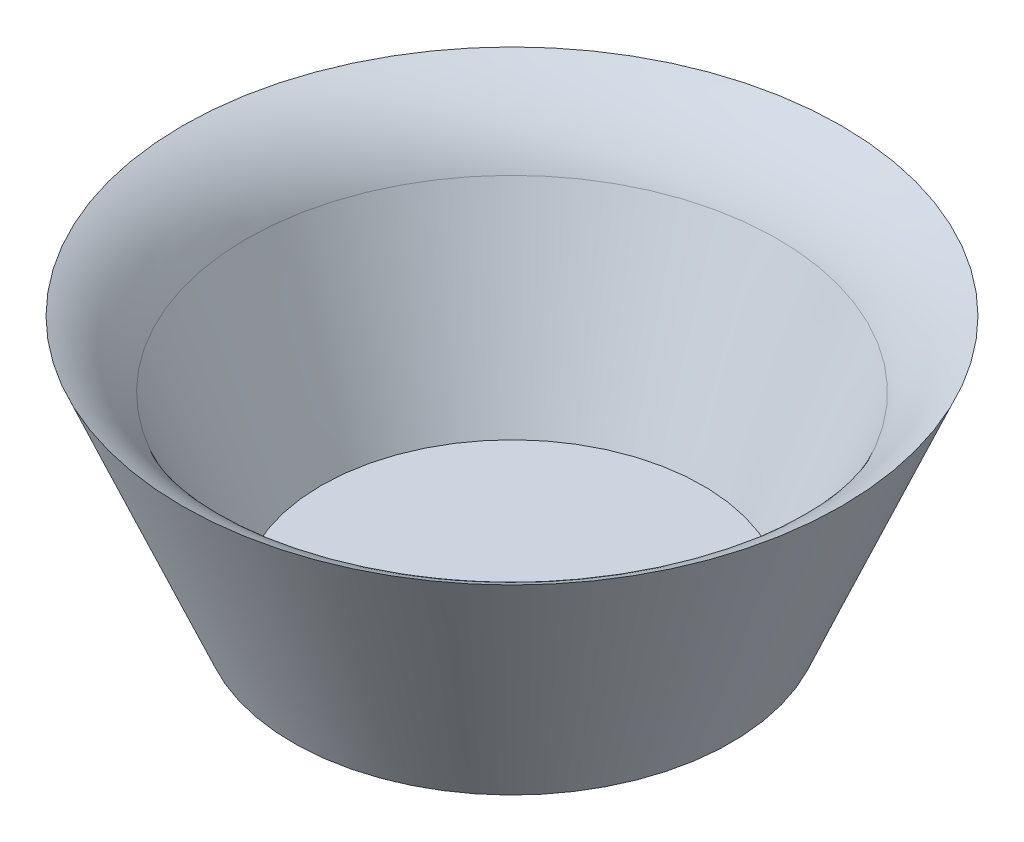
SolidWorks part; units mm, degrees
ref_plane "Front Plane" through (0, 0, 0) normal (0, 0, 1) x (1, 0, 0)
ref_plane "Top Plane" through (0, 0, 0) normal (0, 1, 0) x (1, 0, 0)
ref_plane "Right Plane" through (0, 0, 0) normal (1, 0, 0) x (0, 0, -1)
sketch "Sketch1" plane through (0, 0, 0) normal (0, 0, 1) x (1, 0, 0)
  line L0 (0, -36.8033) -> (0, -71.6035) construction
  line L1 (0, 0) -> (0, -3.5)
  line L2 (0, -3.5) -> (-43, -3.5)
  line L3 (-43, -3.5) -> (-64.6482, 47.5)
  line L4 (-64.6482, 47.5) -> (-57.5869, 47.5)
  line L5 (-57.5869, 47.5) -> (-37.4243, 0)
  line L6 (-37.4243, 0) -> (0, 0)
  line L7 (-65.5997, 28.674) -> (-65.5997, -2.1316) construction
  line L8 (-62, -6.0893) -> (-62, -51.2254) construction
  line L9 (-157.4148, 40.5) -> (-134.7355, 40.5) construction
  circle A0 centre (0, 185.5086) radius 152.4 construction
  point P14 (-61.1175, 47.5)
  point P19 (0, 33.1086)
  dimension "D9" = 304.8
  dimension "D1" = 43
  dimension "D2" = 51
  dimension "D3" = 65.5997
  dimension "D4" = 3.5
  dimension "D5" = 6.5
  dimension "D6" = 113
  dimension "D7" = 62
  dimension "D8" = 7
  dimension "D10" = 152.4
revolve "Revolve1" add sketch "Sketch1" angle 360 about L0
fillet "Fillet2" radius 25 1 edges at (-57.5869, 47.5, 0)
